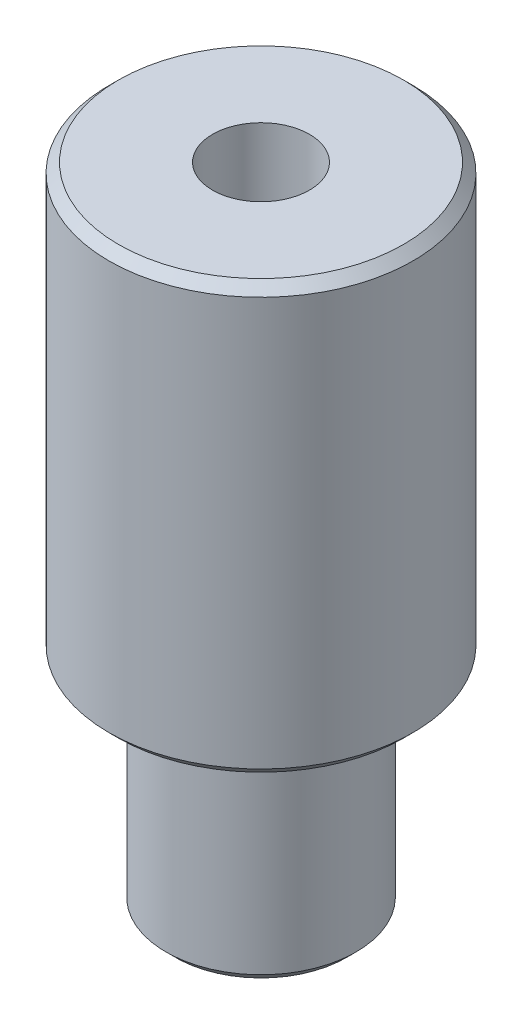
SolidWorks part; units mm, degrees
material "Plain Carbon Steel"
ref_plane "Front Plane" through (0, 0, 0) normal (0, 0, 1) x (1, 0, 0)
ref_plane "Top Plane" through (0, 0, 0) normal (0, 1, 0) x (1, 0, 0)
ref_plane "Right Plane" through (0, 0, 0) normal (1, 0, 0) x (0, 0, -1)
sketch "Sketch1" plane through (0, 0, 0) normal (0, 0, 1) x (1, 0, 0)
  line L0 (0, 0) -> (16, 0)
  line L1 (16, 0) -> (16, -45)
  line L2 (16, -45) -> (10, -45)
  line L3 (10, -45) -> (10, -68)
  line L4 (10, -68) -> (0, -68)
  line L5 (0, -68) -> (0, 0)
  line L6 (0, -73) -> (0, 5) construction
  dimension "D1" = 5
  dimension "D2" = 5
  dimension "D3" = 32
  dimension "D4" = 20
  dimension "D5" = 45
  dimension "D6" = 23
revolve "Revolve1" add sketch "Sketch1" angle 360 about L6
chamfer "Chamfer1" distance 1 angle 45 3 edges at (0, -68, -10) (0, -45, -16) (0, 0, -16)
cosmetic thread "Cosmetic Thread1"
hole_wizard "Ø10.2 (10.2) Diameter Hole1" positions "Sketch5" profile "Sketch2" hole size "Ø10.2" standard "ISO" end condition through all
sketch "Sketch5" plane through (0, 0, 0) normal (0, 1, 0) x (1, 0, 0)
  point P0 (0, 0)
sketch "Sketch2" plane through (0, 0, 0) normal (1, 0, 0) x (0, 0, 1)
  line L0 (0, 0) -> (0, 68)
  line L1 (0, 68) -> (5.1, 68)
  line L2 (5.1, 68) -> (5.1, 0)
  line L5 (5.1, 0) -> (0, 0)
  line L11 (0, -6.35) -> (0, 107.95) construction
  dimension "Thru Hole Dia." = 10.2
  dimension "Thru Hole Depth" = 68
